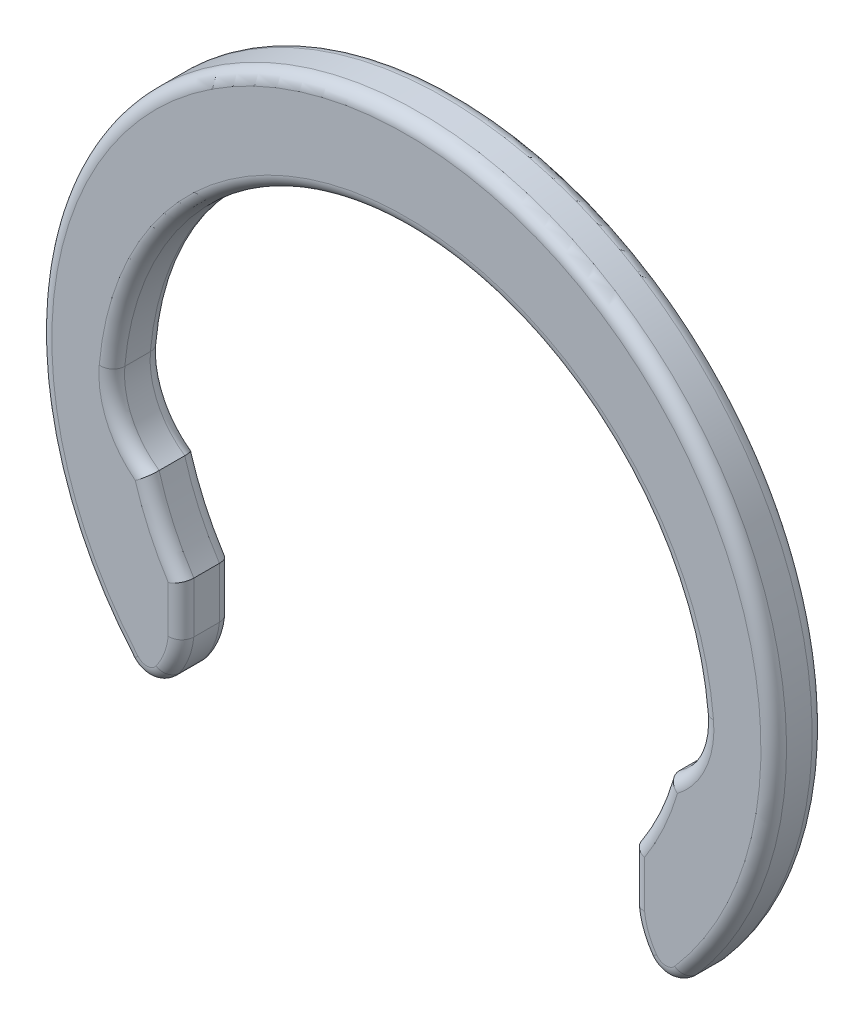
SolidWorks part; units mm, degrees
ref_plane "Front" through (0, 0, 0) normal (0, 0, 1) x (1, 0, 0)
ref_plane "Top" through (0, 0, 0) normal (0, 1, 0) x (1, 0, 0)
ref_plane "Right" through (0, 0, 0) normal (1, 0, 0) x (0, 0, -1)
sketch "Sketch1" plane through (0, 0, 0) normal (0, 0, 1) x (1, 0, 0)
  line L0 (0, 7.175) -> (0, -7.175) construction
  line L1 (-5.275, 0) -> (-7.175, 0) construction
  line L2 (-6.225, 0) -> (-5.275, 0) construction
  line L3 (-5.275, 0) -> (5.275, 0) construction
  line L4 (-4.4017, -4.4017) -> (-4.4017, -2.9069) construction
  line L5 (-5.0789, -1.425) -> (5.0789, -1.425) construction
  line L6 (-5.275, 0) -> (-5.275, -1.425) construction
  line L7 (0, 0) -> (-3.73, -3.73) construction
  line L8 (-3.73, -3.73) -> (-5.0735, -5.0735) construction
  circle A0 centre (0, 0) radius 7.175 construction
  circle A1 centre (0, 0) radius 5.275 construction
  arc A2 (0, 5.275) -> (-5.75, 0) centre (0, -0.4964) ccw construction
  arc A5 (-5.0789, -1.425) -> (-5.75, 0) centre (-4.1879, -0.1349) cw construction
  point P21 (0, 5.275)
  point P23 (0, 7.175)
  dimension "Ring OD" = 14.35
  dimension "D3" = 10.55
  dimension "Max Section" = 1.9
  dimension "D1" = 45
  dimension "D2" = 1.425
  dimension "D4" = 1.425
sketch "Sketch3" plane through (0, 0, 0) normal (0, 1, 0) x (1, 0, 0)
  line L0 (-7.175, 0.5) -> (-7.175, -0.5) construction
  line L3 (-5.275, 0) -> (-7.175, 0) construction
  point P3 (-7.175, 0)
  dimension "Ring Thickness" = 1
sketch "Sketch2" plane through (0, 0, 0) normal (0, 0, 1) x (1, 0, 0)
  line L0 (-4.4017, -4.4017) -> (-4.4017, -3.9035) construction
  line L1 (-4.4017, -3.9035) -> (-4.4017, -3.4052)
  line L2 (-4.4017, -3.4052) -> (-4.4017, -2.9069)
  line L3 (0, 5.275) -> (0, 0) construction
  line L4 (0, 7.175) -> (0, -7.175) construction
  line L5 (-4.4017, -4.4017) -> (-4.6257, -4.6257) construction
  line L6 (0, 7.175) -> (0, 5.275) construction
  line L7 (-4.6257, -4.6257) -> (-4.8496, -4.8496) construction
  line L8 (-4.8496, -4.8496) -> (-5.0735, -5.0735)
  line L9 (-3.73, -3.73) -> (-5.0735, -5.0735) construction
  line L10 (4.4017, -3.4052) -> (4.4017, -2.9069)
  line L11 (4.4017, -3.9035) -> (4.4017, -3.4052)
  line L12 (4.8496, -4.8496) -> (5.0735, -5.0735)
  circle A0 centre (0, 0) radius 7.175 construction
  arc A1 (0, 5.275) -> (-5.75, 0) centre (0, -0.4964) ccw construction
  circle A3 centre (0, 0) radius 5.275 construction
  arc A4 (5.0735, -5.0735) -> (-5.0735, -5.0735) centre (0, 0) ccw
  arc A5 (5.75, 0) -> (-5.75, 0) centre (0, -0.4964) ccw
  arc A6 (-5.75, 0) -> (-5.0789, -1.425) centre (-4.1879, -0.1349) ccw construction
  arc A7 (-5.0789, -1.425) -> (-4.4017, -2.9069) centre (0, 0) ccw
  arc A8 (-4.4017, -3.9035) -> (-4.8496, -4.8496) centre (-5.949, -3.7501) cw
  arc A9 (4.4017, -3.9035) -> (4.8496, -4.8496) centre (5.949, -3.7501) ccw
  arc A10 (5.0789, -1.425) -> (4.4017, -2.9069) centre (0, 0) cw
  arc A11 (5.75, 0) -> (5.0789, -1.425) centre (4.1879, -0.1349) cw
  arc A12 (-5.75, 0) -> (-5.0789, -1.425) centre (-4.1879, -0.1349) ccw
extrude "Boss-Extrude1" add sketch "Sketch2" along normal mid plane 1
fillet "Fillet1" radius 0.475 2 edges at (5.0735, -5.0735, 0) (-5.0735, -5.0735, 0)
fillet "Fillet2" radius 0.25 24 edges at (-5.0495, -4.8534, -0.5) (-4.4939, -4.298, -0.5) (-4.4017, -3.4052, -0.5) (-4.7979, -2.1923, -0.5) (-5.6064, -0.8029, -0.5) (0, 5.275, -0.5) (5.6064, -0.8029, -0.5) (4.7979, -2.1923, -0.5) (4.4017, -3.4052, -0.5) (4.4939, -4.298, -0.5) (5.0495, -4.8534, -0.5) (0, 7.175, -0.5) (4.4017, -3.4052, 0.5) (4.7979, -2.1923, 0.5) (5.6064, -0.8029, 0.5) (0, 5.275, 0.5) (-5.6064, -0.8029, 0.5) (-4.7979, -2.1923, 0.5) (-4.4017, -3.4052, 0.5) (-4.4939, -4.298, 0.5) (-5.0495, -4.8534, 0.5) (0, 7.175, 0.5) (5.0495, -4.8534, 0.5) (4.4939, -4.298, 0.5)
ref_axis "Center Axis 1" through (0, 0, 0.25) along (0, 0, -1)
ref_plane "Contact Plane 1" through (0, 0, 0.5) normal (0, 0, 1) x (1, 0, 0)
ref_plane "Contact Plane 2" through (0, 0, -0.5) normal (0, 0, -1) x (-1, 0, 0)
equation "\"D1@Boss-Extrude1\"=\"Ring Thickness@Sketch3\""
equation "\"D1@Fillet1\" = \"Max Section@Sketch1\" / 4"
equation "\"D2@Sketch1\"=\"Max Section@Sketch1\"*.75"
equation "\"D4@Sketch1\"=\"Max Section@Sketch1\"*.75"
equation "\"D1@Fillet2\"=\"Ring Thickness@Sketch3\"/4"
